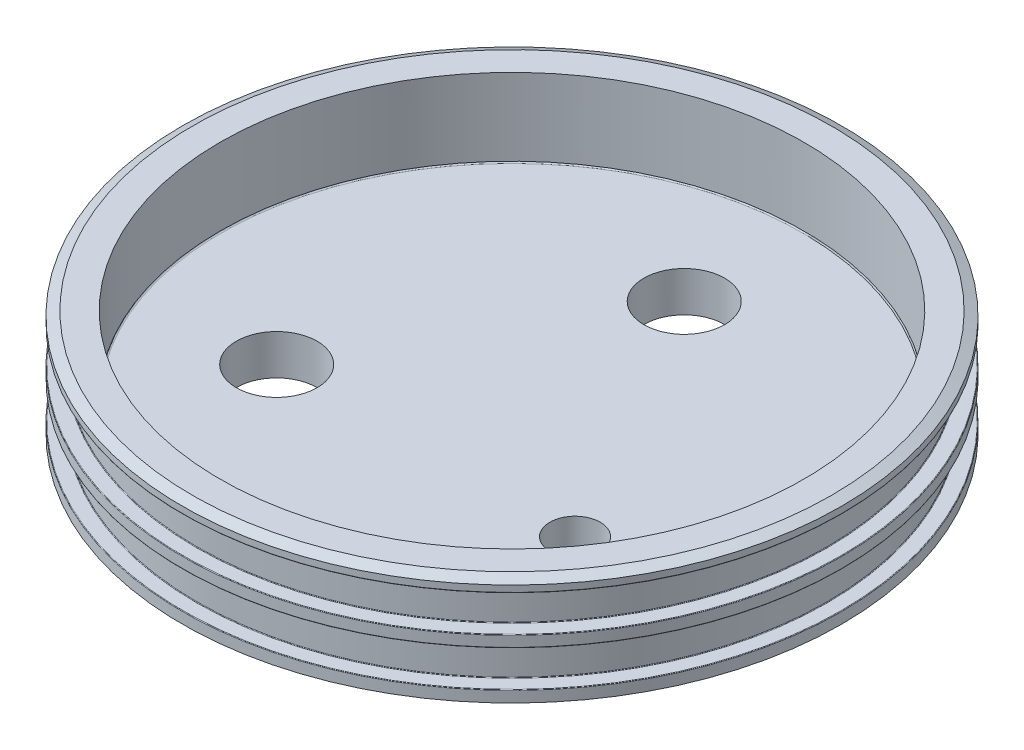
SolidWorks part; units mm, degrees
material "6061-T6 (SS)"
ref_plane "Front Plane" through (0, 0, 0) normal (0, 0, 1) x (1, 0, 0)
ref_plane "Top Plane" through (0, 0, 0) normal (0, 1, 0) x (1, 0, 0)
ref_plane "Right Plane" through (0, 0, 0) normal (1, 0, 0) x (0, 0, -1)
sketch "Sketch1" plane through (0, 0, 0) normal (0, 0, 1) x (1, 0, 0)
  line L0 (0, 48.1922) -> (0, -25.6743) construction
  line L1 (0, 0) -> (72.898, 0)
  line L2 (72.898, 0) -> (72.898, 2.54)
  line L3 (72.898, 2.54) -> (69.6468, 2.54)
  line L4 (69.6468, 2.54) -> (69.6468, 10.541)
  line L5 (69.6468, 10.541) -> (72.898, 10.541)
  line L6 (72.898, 10.541) -> (72.898, 13.081)
  line L7 (72.898, 13.081) -> (69.6468, 13.081)
  line L8 (64.5668, 23.622) -> (64.5668, 6.35)
  line L9 (64.5668, 6.35) -> (0, 6.35)
  line L10 (0, 6.35) -> (0, 0)
  line L11 (69.6468, 13.081) -> (69.6468, 21.082)
  line L12 (69.6468, 21.082) -> (72.898, 21.082)
  line L13 (72.898, 21.082) -> (72.898, 23.622)
  line L14 (72.898, 23.622) -> (64.5668, 23.622)
  dimension "D1" = 145.796
  dimension "D2" = 8.001
  dimension "D5" = 6.35
  dimension "D7" = 8.001
  dimension "D3" = 2.54
  dimension "D4" = 2.54
  dimension "D6" = 69.6468
  dimension "D8" = 5.08
revolve "Revolve1" add sketch "Sketch1" angle 360 about L0
sketch "Sketch6" plane through (0, 0, 0) normal (0, -1, 0) x (1, 0, 0)
  circle A0 centre (0, 0) radius 66.04
  dimension "D1" = 132.08
extrude "Boss-Extrude1" add sketch "Sketch6" along normal blind 2.54
fillet "CNC ID Fillet" radius 0.127 5 edges at (-69.6468, 10.541, 0) (-69.6468, 2.54, 0) (66.04, 0, 0) (-69.6468, 21.082, 0) (-69.6468, 13.081, 0)
fillet "CNC OD Fillet" radius 0.127 5 edges at (-72.898, 10.541, 0) (-72.898, 2.54, 0) (-72.898, 13.081, 0) (-72.898, 21.082, 0) (66.04, -2.54, 0)
chamfer "CNC Chamfers" distance 1.016 angle 65 1 edges at (-72.898, 23.622, 0) first distance on face at (-72.898, 21.209, 0)
fillet "CNC Bore Fillet" radius 0.254 1 edges at (-64.5668, 6.35, 0)
hole_wizard "Pipe Tap Drill for 1/2 Tap - Fill Valve" positions "Sketch13" profile "Sketch14" hole size "1/2" standard "ANSI Inch" end condition through all
sketch "Sketch13" plane through (0, -2.54, 0) normal (0, -1, 0) x (-1, 0, 0)
  point P4 (0, 38.1)
  dimension "D1" = 38.1
sketch "Sketch14" plane through (0, -2.54, -38.1) normal (1, 0, 0) x (0, 0, -1)
  line L0 (0, 0) -> (0, 26.162)
  line L1 (0, 26.162) -> (8.9281, 26.162)
  line L2 (8.9281, 26.162) -> (8.9281, 0)
  line L5 (8.9281, 0) -> (0, 0)
  line L11 (0, -6.35) -> (0, 107.95) construction
  dimension "Thru Hole Dia." = 17.8562
  dimension "Thru Hole Depth" = 26.162
hole_wizard "Pipe Tap Drill for 1/4 Tap - Solenoid Valve" positions "Sketch15" profile "Sketch16" hole size "1/4" standard "ANSI Inch" end condition through all
sketch "Sketch15" plane through (0, -2.54, 0) normal (0, -1, 0) x (-1, 0, 0)
  line L0 (-32.9956, -19.05) -> (0, -19.05) construction
  line L2 (-32.9956, -19.05) -> (0, 0) construction
  point P4 (-32.9956, -19.05)
  dimension "D1" = 30
  dimension "D2" = 38.1
sketch "Sketch16" plane through (32.9956, -2.54, 19.05) normal (1, 0, 0) x (0, 0, -1)
  line L0 (0, 0) -> (0, 26.162)
  line L1 (0, 26.162) -> (5.5626, 26.162)
  line L2 (5.5626, 26.162) -> (5.5626, 0)
  line L5 (5.5626, 0) -> (0, 0)
  line L11 (0, -6.35) -> (0, 107.95) construction
  dimension "Thru Hole Dia." = 11.1252
  dimension "Thru Hole Depth" = 26.162
hole_wizard "Pipe Tap Drill for 1/2 Tap - Cryo Valve" positions "Sketch17" profile "Sketch18" hole size "1/2" standard "ANSI Inch" end condition through all
sketch "Sketch17" plane through (0, -2.54, 0) normal (0, -1, 0) x (-1, 0, 0)
  line L0 (32.9956, -19.05) -> (17.2813, -19.05) construction
  line L2 (32.9956, -19.05) -> (0, 0) construction
  point P4 (32.9956, -19.05)
  dimension "D1" = 30
  dimension "D2" = 38.1
sketch "Sketch18" plane through (-32.9956, -2.54, 19.05) normal (1, 0, 0) x (0, 0, -1)
  line L0 (0, 0) -> (0, 26.162)
  line L1 (0, 26.162) -> (8.9281, 26.162)
  line L2 (8.9281, 26.162) -> (8.9281, 0)
  line L5 (8.9281, 0) -> (0, 0)
  line L11 (0, -6.35) -> (0, 107.95) construction
  dimension "Thru Hole Dia." = 17.8562
  dimension "Thru Hole Depth" = 26.162
equation "\"D6@Sketch1\"=5.484/2"
